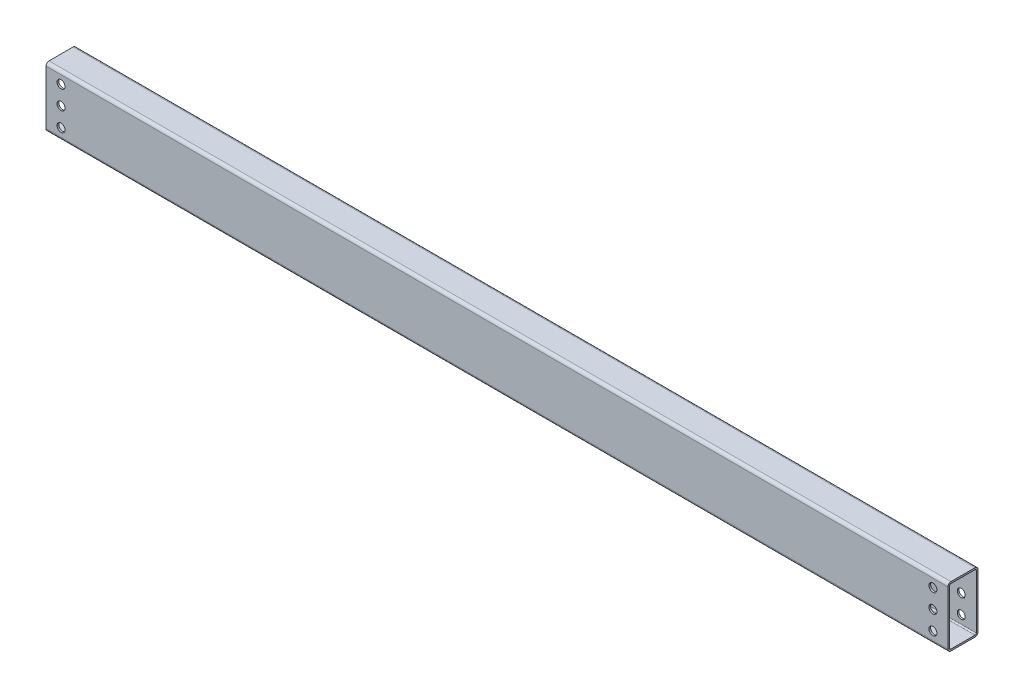
SolidWorks part; units mm, degrees
material "6061-T6 (SS)"
ref_plane "Front" through (0, 0, 0) normal (0, 0, 1) x (1, 0, 0)
ref_plane "Top" through (0, 0, 0) normal (0, 1, 0) x (1, 0, 0)
ref_plane "Right" through (0, 0, 0) normal (1, 0, 0) x (0, 0, -1)
sketch "Sketch1" plane through (0, 0, 0) normal (1, 0, 0) x (0, 0, -1)
  line L0 (10.16, -25.4) -> (-10.16, -25.4)
  line L1 (12.7, -22.86) -> (12.7, 22.86)
  line L2 (10.16, 25.4) -> (-10.16, 25.4)
  line L3 (-12.7, -22.86) -> (-12.7, 22.86)
  line L4 (12.7, -25.4) -> (-12.7, 25.4) construction
  line L5 (12.7, 25.4) -> (-12.7, -25.4) construction
  arc A0 (-10.16, -25.4) -> (-12.7, -22.86) centre (-10.16, -22.86) cw
  arc A1 (10.16, -25.4) -> (12.7, -22.86) centre (10.16, -22.86) ccw
  arc A2 (12.7, 22.86) -> (10.16, 25.4) centre (10.16, 22.86) ccw
  arc A3 (-10.16, 25.4) -> (-12.7, 22.86) centre (-10.16, 22.86) ccw
  point P0 (0, 0)
  point P18 (0, 0)
  point P19 (0, 0)
  dimension "D3" = 2.54
  dimension "D1" = 25.4
  dimension "D2" = 50.8
extrude "Extrude-Thin1" add sketch "Sketch1" along normal mid plane 762 thin thin type one direction reverse wall 1.4478
hole_wizard "1/4 Clearance Hole1" positions "Sketch2" profile "Sketch3" hole size "1/4" standard "ANSI Inch" end condition through all
sketch "Sketch2" plane through (0, 0, -12.7) normal (0, 0, -1) x (-1, 0, 0)
  line L0 (-381, -22.86) -> (-381, 22.86) construction
  line L1 (-381, 25.4) -> (381, 25.4) construction
  line L2 (-381, -25.4) -> (381, -25.4) construction
  line L3 (-368.3, 15.875) -> (-368.3, -15.875) construction
  line L4 (0, 0) -> (0, -37.3791) construction
  point P0 (-368.3, 15.875)
  point P2 (-368.3, -15.875)
  point P15 (-368.3, 0)
  point P23 (368.3, -15.875)
  point P24 (368.3, 0)
  point P25 (368.3, 15.875)
  dimension "D1" = 12.7
  dimension "D2" = 9.525
  dimension "D3" = 9.525
sketch "Sketch3" plane through (368.3, 15.875, -12.7) normal (1, 0, 0) x (0, 1, 0)
  line L0 (0, 0) -> (0, 25.4)
  line L1 (0, 25.4) -> (3.3782, 25.4)
  line L2 (3.3782, 25.4) -> (3.3782, 0)
  line L5 (3.3782, 0) -> (0, 0)
  line L11 (0, -6.35) -> (0, 107.95) construction
  dimension "Thru Hole Dia." = 6.7564
  dimension "Thru Hole Depth" = 25.4
hole_wizard "1/4 Clearance Hole2" positions "Sketch4" profile "Sketch5" hole size "1/4" standard "ANSI Inch" end condition up to next
sketch "Sketch4" plane through (0, 0, -12.7) normal (0, 0, -1) x (-1, 0, 0)
  line L0 (-234.95, 15.875) -> (-234.95, -15.875) construction
  line L2 (-381, 25.4) -> (381, 25.4) construction
  line L3 (-381, -25.4) -> (381, -25.4) construction
  line L4 (0, 0) -> (0, -51.4899) construction
  point P19 (-234.95, 15.875)
  point P21 (-234.95, 0)
  point P23 (-234.95, -15.875)
  point P42 (234.95, -15.875)
  point P43 (234.95, 0)
  point P44 (234.95, 15.875)
  dimension "D1" = 9.525
  dimension "D2" = 9.525
  dimension "D3" = 469.9
sketch "Sketch5" plane through (234.95, 15.875, -12.7) normal (1, 0, 0) x (0, 1, 0)
  line L0 (0, 0) -> (0, 1.4478)
  line L1 (0, 1.4478) -> (3.3782, 1.4478)
  line L2 (3.3782, 1.4478) -> (3.3782, 0)
  line L5 (3.3782, 0) -> (0, 0)
  line L11 (0, -6.35) -> (0, 107.95) construction
  dimension "Thru Hole Dia." = 6.7564
  dimension "Thru Hole Depth" = 1.4478
